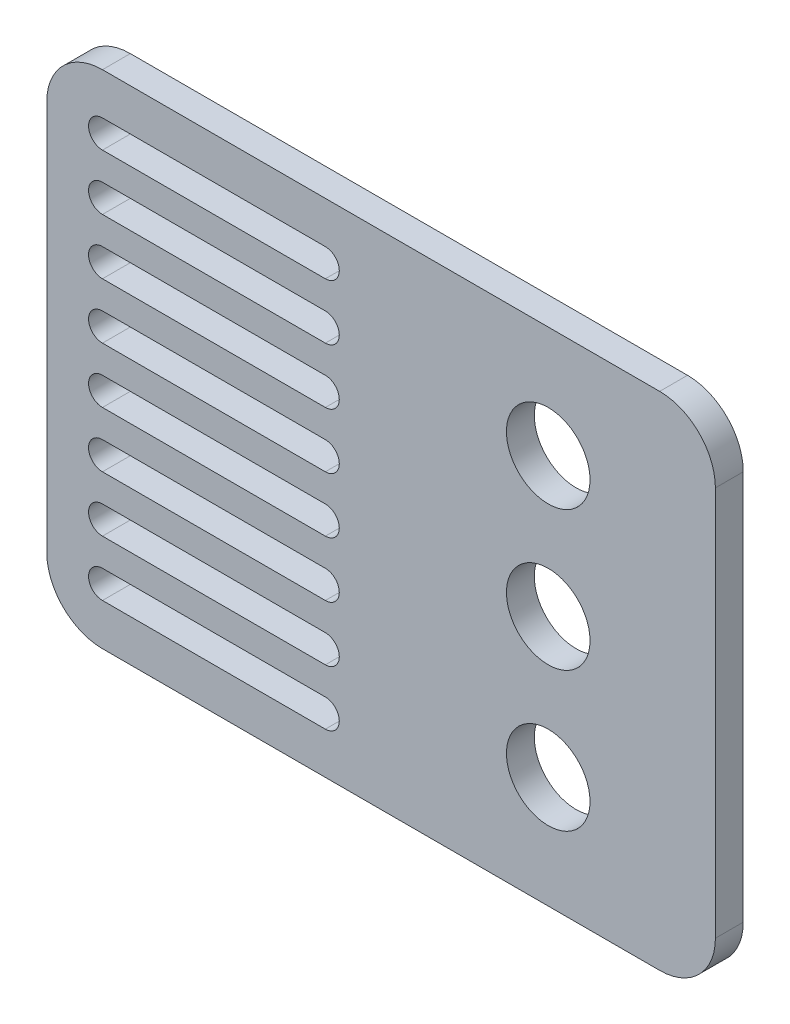
SolidWorks part; units mm, degrees
ref_plane "Front Plane" through (0, 0, 0) normal (0, 0, 1) x (1, 0, 0)
ref_plane "Top Plane" through (0, 0, 0) normal (0, 1, 0) x (1, 0, 0)
ref_plane "Right Plane" through (0, 0, 0) normal (1, 0, 0) x (0, 0, -1)
sketch "Sketch1" plane through (0, 0, 0) normal (0, 0, 1) x (1, 0, 0)
  line L0 (0, 12.7) -> (0, 101.6)
  line L1 (12.7, 114.3) -> (139.7, 114.3)
  line L2 (152.4, 101.6) -> (152.4, 12.7)
  line L3 (139.7, 0) -> (12.7, 0)
  line L4 (12.7, 12.7) -> (63.5, 12.7) construction
  line L5 (12.7, 15.875) -> (63.5, 15.875)
  line L6 (12.7, 9.525) -> (63.5, 9.525)
  line L7 (12.7, 25.4) -> (63.5, 25.4) construction
  line L8 (12.7, 28.575) -> (63.5, 28.575)
  line L9 (12.7, 22.225) -> (63.5, 22.225)
  line L10 (12.7, 38.1) -> (63.5, 38.1) construction
  line L11 (12.7, 41.275) -> (63.5, 41.275)
  line L12 (12.7, 34.925) -> (63.5, 34.925)
  line L13 (12.7, 50.8) -> (63.5, 50.8) construction
  line L14 (12.7, 53.975) -> (63.5, 53.975)
  line L15 (12.7, 47.625) -> (63.5, 47.625)
  line L16 (12.7, 63.5) -> (63.5, 63.5) construction
  line L17 (12.7, 66.675) -> (63.5, 66.675)
  line L18 (12.7, 60.325) -> (63.5, 60.325)
  line L19 (12.7, 76.2) -> (63.5, 76.2) construction
  line L20 (12.7, 79.375) -> (63.5, 79.375)
  line L21 (12.7, 73.025) -> (63.5, 73.025)
  line L22 (12.7, 88.9) -> (63.5, 88.9) construction
  line L23 (12.7, 92.075) -> (63.5, 92.075)
  line L24 (12.7, 85.725) -> (63.5, 85.725)
  line L25 (12.7, 101.6) -> (63.5, 101.6) construction
  line L26 (12.7, 104.775) -> (63.5, 104.775)
  line L27 (12.7, 98.425) -> (63.5, 98.425)
  arc A0 (12.7, 15.875) -> (12.7, 9.525) centre (12.7, 12.7) ccw
  arc A1 (63.5, 9.525) -> (63.5, 15.875) centre (63.5, 12.7) ccw
  arc A2 (152.4, 101.6) -> (139.7, 114.3) centre (139.7, 101.6) ccw
  arc A3 (12.7, 28.575) -> (12.7, 22.225) centre (12.7, 25.4) ccw
  arc A4 (63.5, 22.225) -> (63.5, 28.575) centre (63.5, 25.4) ccw
  arc A5 (12.7, 41.275) -> (12.7, 34.925) centre (12.7, 38.1) ccw
  arc A6 (63.5, 34.925) -> (63.5, 41.275) centre (63.5, 38.1) ccw
  arc A7 (12.7, 53.975) -> (12.7, 47.625) centre (12.7, 50.8) ccw
  arc A8 (63.5, 47.625) -> (63.5, 53.975) centre (63.5, 50.8) ccw
  arc A9 (12.7, 66.675) -> (12.7, 60.325) centre (12.7, 63.5) ccw
  arc A10 (63.5, 60.325) -> (63.5, 66.675) centre (63.5, 63.5) ccw
  arc A11 (12.7, 79.375) -> (12.7, 73.025) centre (12.7, 76.2) ccw
  arc A12 (63.5, 73.025) -> (63.5, 79.375) centre (63.5, 76.2) ccw
  arc A13 (12.7, 92.075) -> (12.7, 85.725) centre (12.7, 88.9) ccw
  arc A14 (63.5, 85.725) -> (63.5, 92.075) centre (63.5, 88.9) ccw
  arc A15 (12.7, 104.775) -> (12.7, 98.425) centre (12.7, 101.6) ccw
  arc A16 (63.5, 98.425) -> (63.5, 104.775) centre (63.5, 101.6) ccw
  arc A17 (12.7, 0) -> (0, 12.7) centre (12.7, 12.7) cw
  arc A18 (0, 101.6) -> (12.7, 114.3) centre (12.7, 101.6) cw
  arc A19 (139.7, 0) -> (152.4, 12.7) centre (139.7, 12.7) ccw
  circle A20 centre (114.3, 25.4) radius 9.525
  circle A21 centre (114.3, 57.15) radius 9.525
  circle A22 centre (114.3, 88.9) radius 9.525
  point P7 (38.1, 12.7)
  point P14 (152.4, 114.3)
  point P19 (38.1, 25.4)
  point P26 (38.1, 38.1)
  point P33 (38.1, 50.8)
  point P40 (38.1, 63.5)
  point P47 (38.1, 76.2)
  point P54 (38.1, 88.9)
  point P61 (38.1, 101.6)
  point P66 (0, 0)
  point P69 (0, 114.3)
  point P72 (152.4, 0)
  point P75 (0, 0)
  point P76 (0, 0)
  dimension "D4" = 12.7
  dimension "D10" = 12.7
  dimension "D11" = 19.05
  dimension "D15" = 25.4
  dimension "D1" = 152.4
  dimension "D2" = 114.3
  dimension "D3" = 50.8
  dimension "D6" = 6.35
  dimension "D7" = 12.7
  dimension "D8" = 12.7
  dimension "D9" = 12.7
  dimension "D12" = 38.1
  dimension "D14" = 31.75
  dimension "D5" = 8
  dimension "D13" = 3
extrude "Boss-Extrude1" add sketch "Sketch1" along normal blind 6.35 contours L3 A19 L2 A2 L1 A18 L0 A17 A22 A21 A20 A1 L6 A0 L5 A4 L9 A3 L8 A6 L12 A5 L11 A8 L15 A7 L14 A10 L18 A9 L17 A12 L21 A11 L20 A14 L24 A13 L23 A16 region at (81.7472, 57.15, 0)
